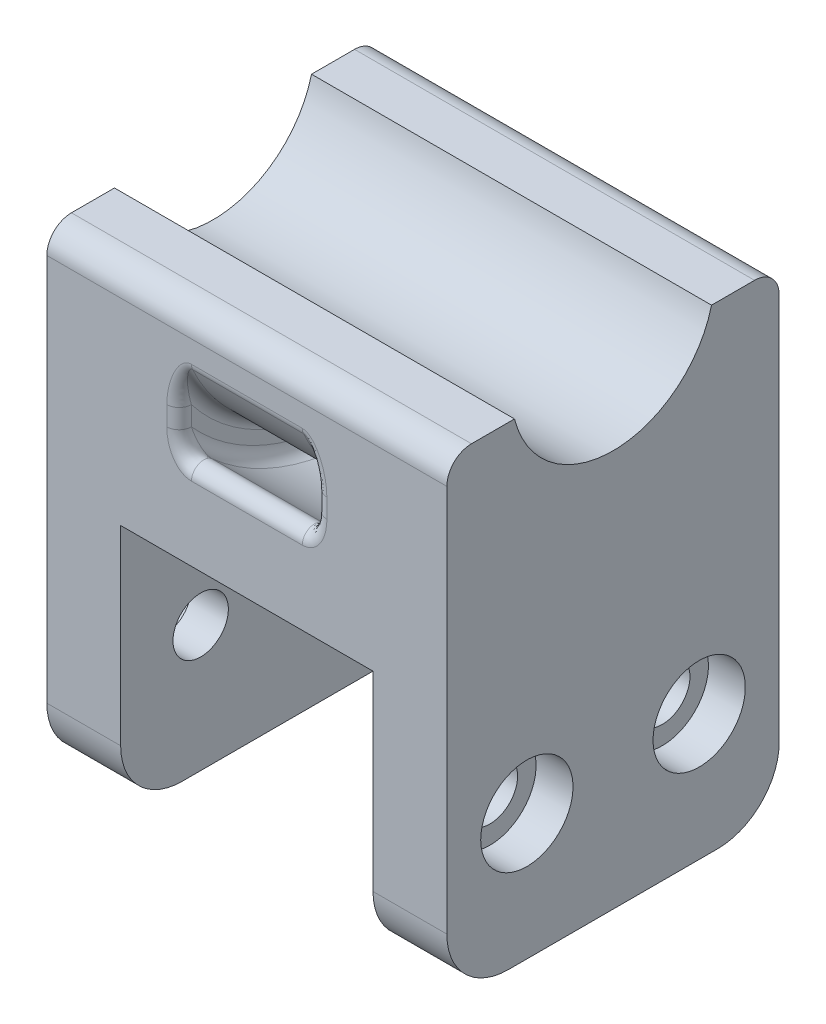
SolidWorks part; units mm, degrees
ref_plane "Спереди" through (0, 0, 0) normal (0, 0, 1) x (1, 0, 0)
ref_plane "Сверху" through (0, 0, 0) normal (0, 1, 0) x (1, 0, 0)
ref_plane "Справа" through (0, 0, 0) normal (1, 0, 0) x (0, 0, -1)
sketch "Эскиз1" plane through (0, 0, 0) normal (0, 1, 0) x (1, 0, 0)
  line L1 (-10.25, 13.5) -> (10.25, 13.5)
  line L2 (-10.25, 13.5) -> (-10.25, -13.5)
  line L3 (-10.25, -13.5) -> (10.25, -13.5)
  line L4 (10.25, 13.5) -> (10.25, -13.5)
  line L5 (-10.25, 13.5) -> (10.25, -13.5) construction
  line L6 (-10.25, -13.5) -> (10.25, 13.5) construction
  point P0 (0, 0)
  dimension "D1" = 27
  dimension "D2" = 20.5
extrude "Бобышка-Вытянуть1" add sketch "Эскиз1" along normal blind 18
sketch "Эскиз2" plane through (-10.25, 0, 0) normal (-1, 0, 0) x (0, 0, 1)
  line L0 (-13.5, 18) -> (13.5, 18) construction
  circle A0 centre (0, 20) radius 8.25
  dimension "D1" = 16.5
  dimension "D2" = 2
extrude "Вырез-Вытянуть1" cut sketch "Эскиз2" against normal through all
sketch "Эскиз3" plane through (0, 0, 0) normal (1, 0, 0) x (0, 0, -1)
  line L0 (-13.5, 18) -> (-13.5, 14) construction
  line L1 (-13.5, 18) -> (-13.5, 0) construction
  circle A0 centre (0, 20) radius 14.7733
  circle A1 centre (0, 20) radius 17.7733
  arc A2 (-8.0039, 18) -> (8.0039, 18) centre (0, 20) ccw construction
  dimension "D1" = 4
  dimension "D2" = 3
extrude "Вырез-Вытянуть2" cut sketch "Эскиз3" against normal mid plane 11
fillet "Скругление1" radius 1 12 edges at (0, 8.4397, -13.5) (5.5, 2.2267, 0) (0, 8.4397, 13.5) (-5.5, 2.2267, 0) (-5.5, 5.2267, 0) (0, 14, 13.5) (5.5, 5.2267, 0) (0, 14, -13.5) (-5.5, 11.2199, 13.5) (-5.5, 11.2199, -13.5) (5.5, 11.2199, 13.5) (5.5, 11.2199, -13.5)
sketch "Эскиз4" plane through (-10.25, 0, 0) normal (-1, 0, 0) x (0, 0, 1)
  line L1 (13.5, -20.5) -> (-13.5, -20.5)
  line L2 (13.5, -20.5) -> (13.5, 0)
  line L3 (13.5, 0) -> (-13.5, 0)
  line L4 (-13.5, -20.5) -> (-13.5, 0)
  line L5 (13.5, -20.5) -> (-13.5, 0) construction
  line L6 (13.5, 0) -> (-13.5, -20.5) construction
  line L11 (-13.5, -10.25) -> (13.5, -10.25) construction
  line L12 (0, 0) -> (0, -20.5) construction
  line L16 (13.5, 18) -> (8.0039, 18)
  line L17 (-8.0039, 18) -> (-13.5, 18)
  line L18 (-13.5, 18) -> (-13.5, 0)
  line L19 (-13.5, 0) -> (13.5, 0)
  line L20 (13.5, 0) -> (13.5, 18)
  line L21 (13.5, 18) -> (8.0039, 18)
  line L22 (-8.0039, 18) -> (-13.5, 18)
  line L23 (-13.5, 18) -> (-13.5, 0)
  line L24 (-13.5, 0) -> (13.5, 0)
  line L25 (13.5, 0) -> (13.5, 18)
  circle A1 centre (-7, -10.25) radius 2.25
  arc A2 (-8.0039, 18) -> (8.0039, 18) centre (0, 20) ccw
  arc A3 (-8.0039, 18) -> (8.0039, 18) centre (0, 20) ccw
  circle A4 centre (7, -10.25) radius 2.25
  point P0 (0, -10.25)
  line M13 (13.5, 18) -> (8.0039, 18)
  arc M14 (8.0039, 18) -> (-8.0039, 18) centre (0, 20) cw
  line M15 (-8.0039, 18) -> (-13.5, 18)
  line M16 (-13.5, 18) -> (-13.5, 0)
  line M17 (-13.5, 0) -> (13.5, 0)
  line M18 (13.5, 0) -> (13.5, 18)
  dimension "D4" = 4.5
  dimension "D1" = 20.5
  dimension "D3" = 14
extrude "Бобышка-Вытянуть2" add sketch "Эскиз4" along normal blind 6 contours M18 M13 M14 M15 M16 M17 | L4 L1 L2 A4 A1 M17 region at (-10.25, -10.25, 0) region at (-10.25, 7.8469, 0)
sketch "Эскиз5" plane through (-16.25, 0, 0) normal (-1, 0, 0) x (0, 0, 1)
  circle A0 centre (-7, -10.25) radius 3.75
  circle A1 centre (7, -10.25) radius 3.75
  dimension "D1" = 7.5
  dimension "D2" = 7.5
extrude "Вырез-Вытянуть3" cut sketch "Эскиз5" against normal blind 3
fillet "Скругление2" radius 5 2 edges at (-13.25, -20.5, 13.5) (-13.25, -20.5, -13.5)
mirror "Зеркальное отражение1" about plane through (0, 0, 0) normal (1, 0, 0) of "Бобышка-Вытянуть2", "Вырез-Вытянуть3", "Скругление2"
fillet "Скругление3" radius 2 2 edges at (0, 18, 13.5) (0, 18, -13.5)
equation "\"print_offset\"= 0.5"
equation "\"screw_m5_d\"= 4"
equation "\"screw_m5_hh_d\"= 7"
equation "\"nut_m5_d\"= 7.9"
equation "\"nut_m5_h\"= 3.9"
equation "\"tube_d\"= 16"
equation "\"tube_tape_d\"= 3"
equation "\"tube_tape_h\"= 11"
equation "\"D1@Эскиз2\"=\"tube_d\"+\"print_offset\""
equation "\"D2@Эскиз3\"=\"tube_tape_d\""
equation "\"D1@Вырез-Вытянуть2\"=\"tube_tape_h\""
equation "\"D1@Эскиз4\"=\"print_offset\"+20"
equation "\"D3@Эскиз4\"=14"
equation "\"D4@Эскиз4\"=\"screw_m5_d\"+\"print_offset\""
equation "\"D1@Эскиз5\"=\"screw_m5_hh_d\"+\"print_offset\""
equation "\"D2@Эскиз5\"=\"D1@Эскиз5\""
equation "\"D2@Эскиз1\"=\"print_offset\"+20"
